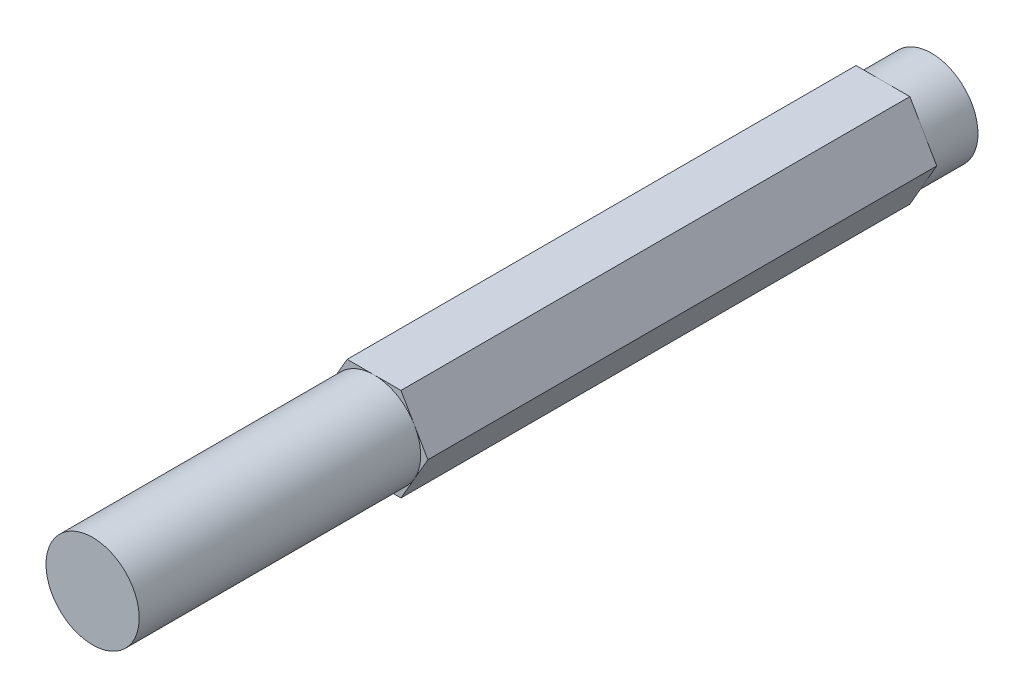
SolidWorks part; units mm, degrees
material "ASTM A36 Steel"
ref_plane "Front Plane" through (0, 0, 0) normal (0, 0, 1) x (1, 0, 0)
ref_plane "Top Plane" through (0, 0, 0) normal (0, 1, 0) x (1, 0, 0)
ref_plane "Right Plane" through (0, 0, 0) normal (1, 0, 0) x (0, 0, -1)
sketch "Sketch1" plane through (0, 0, 0) normal (0, 0, 1) x (1, 0, 0)
  line L1 (7.3323, 0) -> (3.6662, 6.35)
  line L2 (3.6662, 6.35) -> (-3.6662, 6.35)
  line L3 (-3.6662, 6.35) -> (-7.3323, 0)
  line L4 (-7.3323, 0) -> (-3.6662, -6.35)
  line L5 (-3.6662, -6.35) -> (3.6662, -6.35)
  line L6 (3.6662, -6.35) -> (7.3323, 0)
  circle A0 centre (0, 0) radius 6.35
  dimension "D1" = 6.35
extrude "Boss-Extrude1" add sketch "Sketch1" along normal blind 114.3 contours A0 | A0 L1 L2 | L2 L3 L4 L5 L6 L1 region at (3.2816, 5.6838, 0) region at (0, 0, 0)
extrude "Cut-Extrude1" cut sketch "Sketch1<3>" along normal blind 6.604 contours A0 L3 L4 | A0 L2 L3 | A0 L1 L2 | A0 L6 L1 | A0 L5 L6 | A0 L4 L5 region at (6.5631, 0, 0) region at (3.2816, 5.6838, 0) region at (3.2816, -5.6838, 0) region at (-3.2816, 5.6838, 0) region at (-3.2816, -5.6838, 0) region at (-6.5631, 0, 0)
sketch "Sketch1<3>" plane through (0, 0, 0) normal (0, 0, 1) x (1, 0, 0) same geometry as "Sketch1"
ref_plane "Plane1" through (0, 0, 75.946) normal (0, 0, -1) x (-1, 0, 0)
sketch "Sketch3" plane through (0, 0, 75.946) normal (0, 0, -1) x (-1, 0, 0)
  line L1 (-3.6662, 6.35) -> (-7.3323, 0)
  line L2 (-7.3323, 0) -> (-3.6662, -6.35)
  line L3 (-3.6662, -6.35) -> (3.6662, -6.35)
  line L4 (3.6662, -6.35) -> (7.3323, 0)
  line L5 (7.3323, 0) -> (3.6662, 6.35)
  line L6 (3.6662, 6.35) -> (-3.6662, 6.35)
  circle A0 centre (0, 0) radius 6.35
  circle A1 centre (0, 0) radius 6.35 construction
extrude "Cut-Extrude3" cut sketch "Sketch3" against normal through all contours A0 L3 L4 | A0 L2 L3 | A0 L1 L2 | A0 L6 L1 | A0 L5 L6 | A0 L4 L5 region at (3.2816, 5.6838, 75.946) region at (6.5631, 0, 75.946) region at (-3.2816, 5.6838, 75.946) region at (3.2816, -5.6838, 75.946) region at (-6.5631, 0, 75.946) region at (-3.2816, -5.6838, 75.946)
